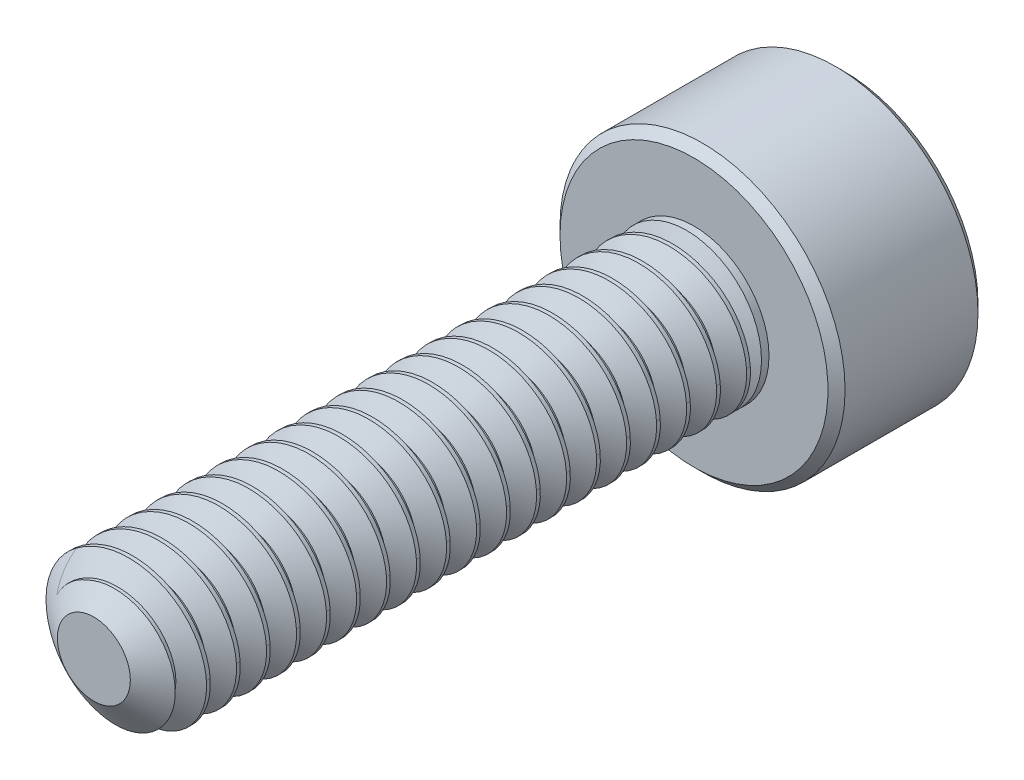
SolidWorks part; units mm, degrees
ref_plane "Front Plane" through (0, 0, 0) normal (0, 0, 1) x (1, 0, 0)
ref_plane "Top Plane" through (0, 0, 0) normal (0, 1, 0) x (1, 0, 0)
ref_plane "Right Plane" through (0, 0, 0) normal (1, 0, 0) x (0, 0, -1)
sketch "Sketch1" plane through (0, 0, 0) normal (0, 0, 1) x (1, 0, 0)
  circle A0 centre (0, 0) radius 1
  dimension "OD" = 2
extrude "Extrude1" add sketch "Sketch1" against normal blind 8
sketch "Sketch2" plane through (0, 0, 0) normal (0, 0, 1) x (1, 0, 0)
  circle A0 centre (0, 0) radius 1 construction
  circle A1 centre (0, 0) radius 1
curve "Helix/Spiral1" pitch 0.4 height 8.4 radius 1 centre (0, 0, 0) axis (0, 0, -1) start towards (0, 1, 0) parameters "pitch"=0.4
sketch "Sketch3" plane through (0, 0, 0) normal (1, 0, 0) x (0, 0, -1)
  line L0 (-0.35, 1) -> (-0.2, 0.7402)
  line L1 (-0.2, 0.7402) -> (-0.15, 0.7402)
  line L2 (-0.15, 0.7402) -> (0, 1)
  line L3 (-0.35, 1) -> (0, 1)
  line L4 (-0.175, 1) -> (-0.175, 0.7402) construction
  line L5 (-0.275, 0.8701) -> (-0.075, 0.8701) construction
  line L6 (0, 1) -> (0, -1) construction
  line L7 (0, -1) -> (8, -1) construction
  point P11 (1.8, -1)
  dimension "D1" = 0.05
  dimension "D2" = 0.2
  dimension "D3" = 60
  dimension "D4" = 1.8
sweep "Cut-Sweep1" cut profiles "Sketch3" path "Helix/Spiral1" align with end faces yes
sketch "Sketch4" plane through (0, 0, 0) normal (1, 0, 0) x (0, 0, -1)
  line L0 (0.3598, 1) -> (0, 0.4862)
  line L1 (0, 0.4862) -> (0, 1)
  line L2 (0.3598, 1) -> (0, 1)
  line L3 (-0.35, 1) -> (0, 1) construction
  line L4 (0, 0) -> (7.0209, 0) construction
  dimension "D1" = 55
  dimension "D2" = 0.254
revolve "Cut-Revolve1" cut sketch "Sketch4" angle 360 about L4
sketch "Sketch5" plane through (0, 0, 0) normal (1, 0, 0) x (0, 0, -1)
  line L0 (8, -0.7473) -> (8, 0.7135) construction
  line L1 (8, 1) -> (0.1203, 1)
  line L2 (8, 1) -> (8, 0)
  line L3 (8, 0) -> (0.0001, 0)
  line L4 (0.0001, 0.6698) -> (0.0001, 0)
  line L5 (0.1203, 1) -> (0.0001, 0.6698)
  line L6 (0, 0) -> (9.9695, 0) construction
  point P3 (0.0001, 1)
  point P10 (0.0001, 1)
  dimension "D1" = 0.3302
  dimension "Thread min" = 0.0001
  dimension "D3" = 20
revolve "partially thread" [suppressed] add sketch "Sketch5" angle 360 about L6
sketch "Sketch6" plane through (0, 0, -8) normal (0, 0, -1) x (-1, 0, 0)
  circle A0 centre (0, 0) radius 1.9
  dimension "head dia" = 3.8
extrude "Extrude2" add sketch "Sketch6" along normal blind 2
sketch "Sketch7" plane through (0, 0, -10) normal (0, 0, -1) x (-1, 0, 0)
  line L1 (0, 0.866) -> (-0.75, 0.433)
  line L2 (-0.75, 0.433) -> (-0.75, -0.433)
  line L3 (-0.75, -0.433) -> (0, -0.866)
  line L4 (0, -0.866) -> (0.75, -0.433)
  line L5 (0.75, -0.433) -> (0.75, 0.433)
  line L6 (0.75, 0.433) -> (0, 0.866)
  circle A0 centre (0, 0) radius 0.75 construction
  dimension "hex dia" = 1.5
extrude "Cut-Extrude1" cut sketch "Sketch7" against normal blind 1.125
sketch "Sketch8" plane through (0, 0, -10) normal (0, 0, -1) x (-1, 0, 0)
  circle A0 centre (0, 0) radius 0.866
extrude "Cut-Extrude2" cut sketch "Sketch8" against normal through all draft 45
chamfer "Chamfer1" distance 0.114 angle 45 2 edges at (-1.9, 0, -10) (-1.9, 0, -8)
sketch "Sketch9" plane through (0, 0, 0) normal (1, 0, 0) x (0, 0, -1)
  line L0 (0, 1) -> (0, -1) construction
  line L1 (2.2, 1) -> (2.2, -1) construction
  dimension "D1" = 2.2
sketch "Sketch10" plane through (0, 0, 0) normal (1, 0, 0) x (0, 0, -1)
  line L0 (8, 1) -> (8, 0)
  line L1 (8, 1) -> (7.9, 1)
  line L2 (7.9, 1) -> (7.4858, 0)
  line L3 (8, 0) -> (7.4858, 0)
  line L4 (8, 1.786) -> (8, -1.786) construction
  dimension "D1" = 22.5
  dimension "D2" = 0.1
revolve "Revolve1" add sketch "Sketch10" angle 360 about L3
equation "\"D3@Helix/Spiral1\" = \"screw length@Extrude1\"+\"pitch@Helix/Spiral1\""
equation "\"D1@Sketch3\" = \"pitch@Helix/Spiral1\"*.125"
equation "\"D2@Sketch3\" = \"pitch@Helix/Spiral1\"*.5"
equation "\"D1@Cut-Extrude1\" = \"hex dia@Sketch7\"*.75"
equation "\"D1@Chamfer1\" = \"head dia@Sketch6\"*.03"
equation "\"D1@Sketch9\" = \"pitch@Helix/Spiral1\"*5.5"
equation "\"D2@Sketch10\" = \"pitch@Helix/Spiral1\"*.25"
equation "\"D4@Sketch3\" = \"pitch@Helix/Spiral1\"*4.50"
